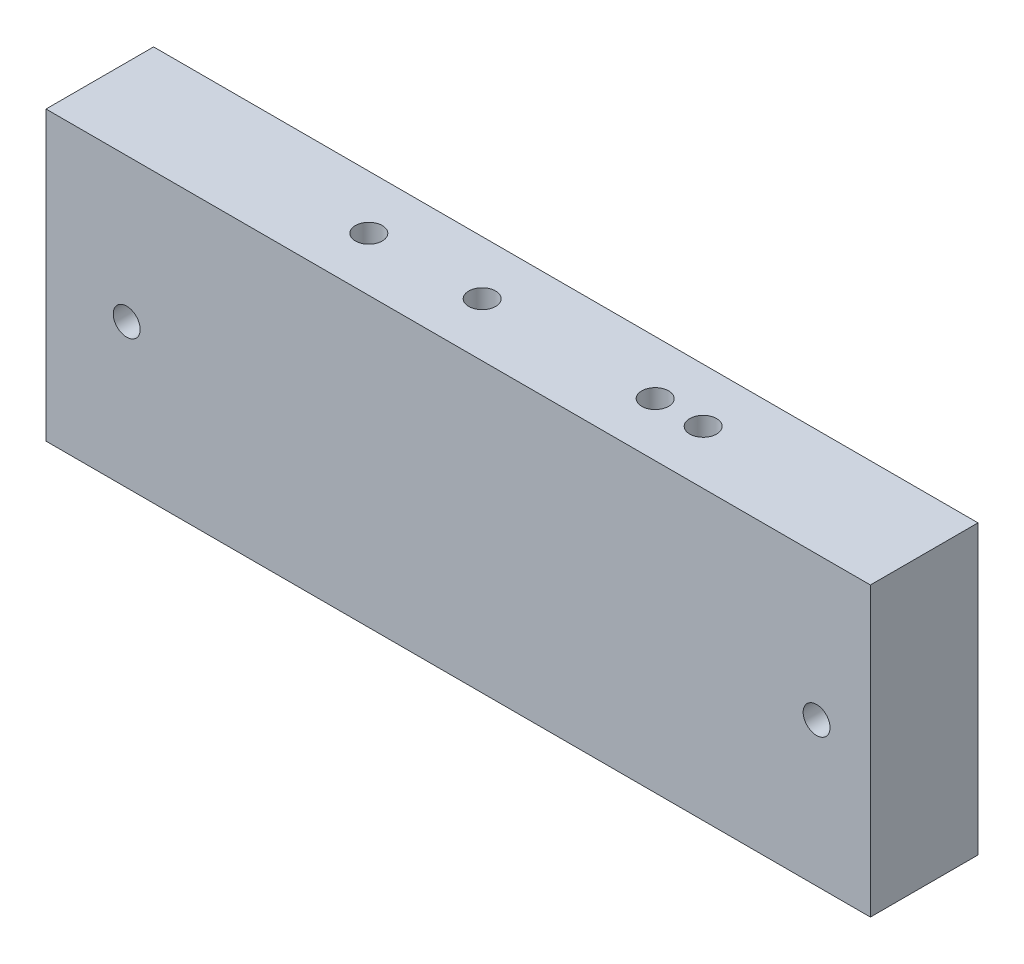
SolidWorks part; units mm, degrees
material "Beech"
ref_plane "Front Plane" through (0, 0, 0) normal (0, 0, 1) x (1, 0, 0)
ref_plane "Top Plane" through (0, 0, 0) normal (0, 1, 0) x (1, 0, 0)
ref_plane "Right Plane" through (0, 0, 0) normal (1, 0, 0) x (0, 0, -1)
sketch "Sketch1" plane through (0, 0, 0) normal (0, 0, 1) x (1, 0, 0)
  line L0 (-244.0045, -53) -> (-244.0045, -19) construction
  line L1 (-341.3045, -19.05) -> (-244.0045, -19.05)
  line L2 (-341.3045, -19.05) -> (-341.3045, -53)
  line L3 (-341.3045, -53) -> (-244.0045, -53)
  line L4 (-244.0045, -19.05) -> (-244.0045, -53)
  dimension "D2" = 33.95
extrude "Boss-Extrude1" add sketch "Sketch1" against normal blind 12.7
hole_wizard "Hole1" positions "Sketch2" profile "Sketch3" legacy
sketch "Sketch2" plane through (-124.0045, 0, 78.4757) normal (0, 1, 0) x (-1, 0, 0)
  line L21 (0, 20.1243) -> (0, 66.1243) construction
  point P37 (126.35, 72.4743)
  point P42 (146.0833, -84.8257)
  point P44 (172.1667, -84.8257)
  point P63 (126.35, -54.3757)
  point P65 (126.35, 42.0243)
  point P76 (-172.1667, -84.8257)
  point P77 (-146.0833, -84.8257)
  point P78 (-126.35, -54.3757)
  point P79 (-126.35, 42.0243)
  point P80 (-126.35, 72.4743)
sketch "Sketch3" plane through (-250.3545, 0, 150.95) normal (1, 0, 0) x (0, 0, 1)
  line L0 (0, 0) -> (0, 32.7039)
  line L1 (0, 32.7039) -> (1.5875, 31.75)
  line L2 (1.5875, 31.75) -> (1.5875, 4.0177)
  line L3 (1.5875, 4.0177) -> (5.08, 0)
  line L4 (5.08, 0) -> (0, 0)
  line L5 (0, -14.3089) -> (0, 102.4216) construction
  line L6 (0, 32.7039) -> (-1.5875, 31.75) construction
  line L7 (-1.5875, 4.0177) -> (-5.08, 0) construction
  dimension "Diameter" = 3.175
  dimension "Depth" = 31.75
  dimension "C-Sink Diameter" = 10.16
  dimension "C-Sink Angle" = 82
  dimension "Drill Angle" = 118
hole_wizard "Hole2" positions "Sketch4" profile "Sketch5" legacy
sketch "Sketch4" plane through (-124.0045, -72.05, 78.4757) normal (0, -1, 0) x (1, 0, 0)
  line L21 (0, 20.1243) -> (0, 66.1243) construction
  point P37 (126.35, 72.4743)
  point P42 (146.0833, -84.8257)
  point P44 (172.1667, -84.8257)
  point P63 (126.35, -54.3757)
  point P65 (126.35, 42.0243)
  point P76 (-172.1667, -84.8257)
  point P77 (-146.0833, -84.8257)
  point P78 (-126.35, -54.3757)
  point P79 (-126.35, 42.0243)
  point P80 (-126.35, 72.4743)
sketch "Sketch5" plane through (2.3455, -72.05, 150.95) normal (1, 0, 0) x (0, 0, -1)
  line L0 (0, 0) -> (0, 32.7039)
  line L1 (0, 32.7039) -> (1.5875, 31.75)
  line L2 (1.5875, 31.75) -> (1.5875, 4.0177)
  line L3 (1.5875, 4.0177) -> (5.08, 0)
  line L4 (5.08, 0) -> (0, 0)
  line L5 (0, -14.3089) -> (0, 102.4216) construction
  line L6 (0, 32.7039) -> (-1.5875, 31.75) construction
  line L7 (-1.5875, 4.0177) -> (-5.08, 0) construction
  dimension "Diameter" = 3.175
  dimension "Depth" = 31.75
  dimension "C-Sink Diameter" = 10.16
  dimension "C-Sink Angle" = 82
  dimension "Drill Angle" = 118
hole_wizard "Hole5" positions "Sketch8" profile "Sketch9" legacy
sketch "Sketch8" plane through (-124.0045, -208.2867, -12.7) normal (0, 0, -1) x (-1, 0, 0)
  line L0 (120, 172.2617) -> (217.3, 172.2617) construction
  point P8 (126.35, 172.2617)
  point P10 (207.775, 172.2617)
sketch "Sketch9" plane through (-331.7795, -36.025, -12.7) normal (1, 0, 0) x (0, 1, 0)
  line L0 (0, 0) -> (0, 32.7039)
  line L1 (0, 32.7039) -> (1.5875, 31.75)
  line L2 (1.5875, 31.75) -> (1.5875, 4.0177)
  line L3 (1.5875, 4.0177) -> (5.08, 0)
  line L4 (5.08, 0) -> (0, 0)
  line L5 (0, -14.3089) -> (0, 102.4216) construction
  line L6 (0, 32.7039) -> (-1.5875, 31.75) construction
  line L7 (-1.5875, 4.0177) -> (-5.08, 0) construction
  dimension "Diameter" = 3.175
  dimension "Depth" = 31.75
  dimension "C-Sink Diameter" = 10.16
  dimension "C-Sink Angle" = 82
  dimension "Drill Angle" = 118
hole_wizard "Hole6" positions "Sketch10" profile "Sketch11" legacy
sketch "Sketch10" plane through (-124.0045, -6.35, 78.4757) normal (0, 1, 0) x (-1, 0, 0)
  line L12 (0, 0) -> (0, 66.1243) construction
  line L17 (120, -84.8257) -> (217.3, -84.8257) construction
  line L21 (-217.3, -84.8257) -> (-120, -84.8257) construction
  point P0 (-207.775, 244.1214)
  point P3 (-207.775, 136.589)
  point P6 (-207.775, 48.5243)
  point P9 (-185.55, -84.8257)
  point P12 (-151.75, -84.8257)
  point P15 (-94.6, 72.4743)
  point P21 (94.6, 72.4743)
  point P24 (151.75, -84.8257)
  point P27 (185.55, -84.8257)
  point P30 (207.775, 48.5243)
  point P33 (207.775, 136.589)
  point P36 (207.775, 244.1214)
  point P39 (166.7958, 213.0704)
  point P42 (40.9792, 213.0704)
  point P45 (-40.9792, 213.0704)
  point P48 (-166.7958, 213.0704)
  point P51 (0, 104.2243)
  point P54 (0, 213.0704)
  point P57 (0, 323.4664)
  point P80 (-126.35, 34.5243)
  point P82 (-126.35, -46.8757)
  point P96 (126.35, -46.8757)
  point P97 (126.35, 34.5243)
  dimension "D4" = 31.75
  dimension "D5" = 31.75
sketch "Sketch11" plane through (83.7705, -6.35, 322.5971) normal (1, 0, 0) x (0, 0, 1)
  line L0 (0, 0) -> (0, 32.7039)
  line L1 (0, 32.7039) -> (1.5875, 31.75)
  line L2 (1.5875, 31.75) -> (1.5875, 4.0177)
  line L3 (1.5875, 4.0177) -> (5.08, 0)
  line L4 (5.08, 0) -> (0, 0)
  line L5 (0, -14.3089) -> (0, 102.4216) construction
  line L6 (0, 32.7039) -> (-1.5875, 31.75) construction
  line L7 (-1.5875, 4.0177) -> (-5.08, 0) construction
  dimension "Diameter" = 3.175
  dimension "Depth" = 31.75
  dimension "C-Sink Diameter" = 10.16
  dimension "C-Sink Angle" = 82
  dimension "Drill Angle" = 118
